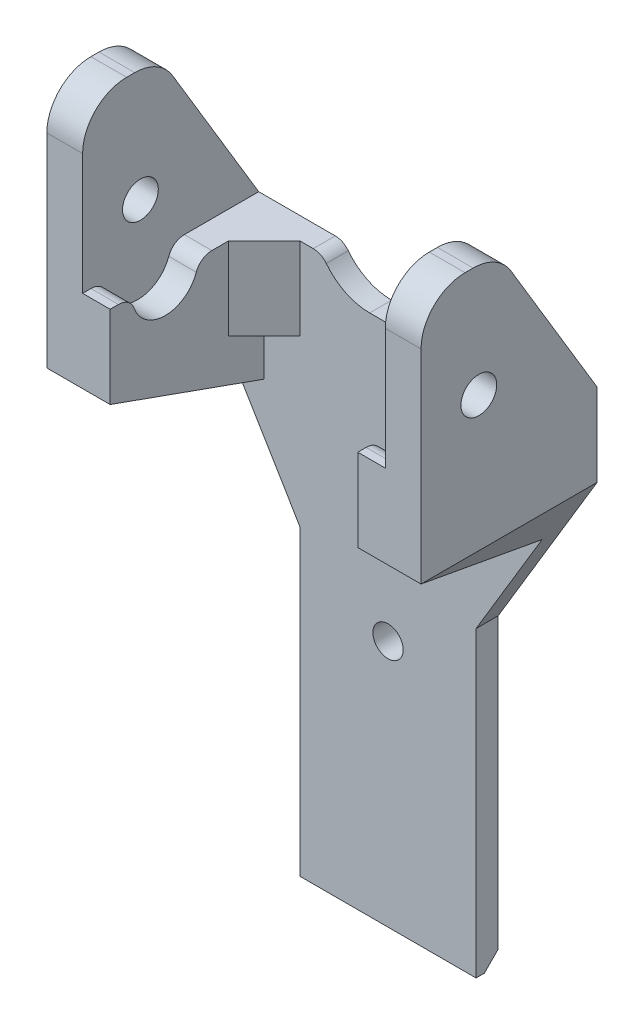
SolidWorks part; units mm, degrees
ref_plane "Plan de face" through (0, 0, 0) normal (0, 0, 1) x (1, 0, 0)
ref_plane "Plan de dessus" through (0, 0, 0) normal (0, 1, 0) x (1, 0, 0)
ref_plane "Plan de droite" through (0, 0, 0) normal (1, 0, 0) x (0, 0, -1)
sketch "Esquisse1" plane through (0, 0, 0) normal (0, 0, 1) x (1, 0, 0)
  line L1 (0, 0) -> (32, 0)
  line L2 (0, 0) -> (0, 100)
  line L3 (0, 100) -> (32, 100)
  line L4 (32, 0) -> (32, 100)
  dimension "D1" = 32
  dimension "D2" = 100
extrude "Boss.-Extru.1" add sketch "Esquisse1" along normal blind 4
chamfer "Chanfrein1" distance 2.5 angle 45 1 edges at (16, 0, 0)
fillet "Congé1" [suppressed] radius 10
sketch "Esquisse2" plane through (0, 0, 0) normal (0, 0, -1) x (-1, 0, 0)
  line L0 (-32, 2.5) -> (-32, 100) construction
  line L1 (-32, 85) -> (-50, 85)
  line L2 (-32, 85) -> (-32, 130)
  line L3 (-32, 130) -> (-50, 130)
  line L4 (-50, 85) -> (-50, 130)
  line L5 (-16, 100) -> (-16, 125.1629) construction
  line L6 (-32, 100) -> (0, 100) construction
  line L7 (18, 85) -> (18, 130)
  line L8 (0, 130) -> (18, 130)
  line L9 (0, 85) -> (0, 130)
  line L10 (0, 85) -> (18, 85)
  dimension "D1" = 15
  dimension "D2" = 18
  dimension "D3" = 30
extrude "Boss.-Extru.2" add sketch "Esquisse2" against normal blind 32
sketch "Esquisse3" plane through (-18, 0, 0) normal (-1, 0, 0) x (0, 0, 1)
  line L0 (32, 85) -> (0, 85) construction
  line L1 (4, 85) -> (4, 0) construction
  circle A0 centre (21.5, 109.5) radius 3.25
  dimension "D1" = 6.5
  dimension "D2" = 24.5
  dimension "D3" = 17.5
extrude "Enlèv. mat.-Extru.1" cut sketch "Esquisse3" against normal through all both and the other way through all
sketch "Esquisse4" plane through (0, 0, 32) normal (0, 0, 1) x (1, 0, 0)
  line L0 (-11.5, 100) -> (43.5, 100)
  line L1 (32, 100) -> (0, 100) construction
  line L2 (43.5, 100) -> (43.5, 132)
  line L3 (43.5, 132) -> (-11.5, 132)
  line L4 (16, 132) -> (16, 100) construction
  line L5 (-11.5, 100) -> (-11.5, 132)
  dimension "D1" = 55
  dimension "D2" = 32
extrude "Enlèv. mat.-Extru.2" cut sketch "Esquisse4" against normal through all both and the other way through all
sketch "Esquisse5" plane through (0, 100, 0) normal (0, 1, 0) x (1, 0, 0)
  line L0 (16, -4) -> (16, -34) construction
  line L1 (32, -4) -> (0, -4) construction
  line L2 (-6.5, -34) -> (38.5, -34)
  line L3 (38.5, -34) -> (38.5, -10.5)
  line L4 (38.5, -10.5) -> (-6.5, -10.5)
  line L5 (-6.5, -34) -> (-6.5, -10.5)
  point P8 (16, -10.5)
  dimension "D1" = 30
  dimension "D2" = 6.5
  dimension "D3" = 45
extrude "Enlèv. mat.-Extru.3" cut sketch "Esquisse5" against normal through all both and the other way through all
chamfer "Chanfrein2" distance 6.5 angle 45 2 edges at (0, 92.5, 10.5) (32, 92.5, 10.5)
sketch "Esquisse6" plane through (-6.5, 0, 0) normal (1, 0, 0) x (0, 0, -1)
  line L0 (0, 100) -> (-32, 100) construction
  line L1 (-32, 100) -> (-32, 130) construction
  line L2 (-28, 100) -> (-16, 100)
  arc A0 (-28, 100) -> (-16, 100) centre (-22, 100) ccw
  dimension "D1" = 6
  dimension "D2" = 10
extrude "Enlèv. mat.-Extru.4" cut sketch "Esquisse6" against normal up to vertex (5 mm away) up to point (-11.5, 100, 32)
extrude "Enlèv. mat.-Extru.6" cut sketch "Esquisse6<2>" along normal up to surface (50 mm away) from surface up to face at (43.5, 115, 16) starting at face at (38.5, 92.5, 21.25)
sketch "Esquisse6<2>" plane through (-6.5, 0, 0) normal (1, 0, 0) x (0, 0, -1) same geometry as "Esquisse6"
fillet "Congé2" radius 3 4 edges at (-9, 100, 28) (-9, 100, 16) (41, 100, 28) (41, 100, 16)
sketch "Esquisse7" plane through (50, 0, 0) normal (1, 0, 0) x (0, 0, -1)
  line L0 (0, 100) -> (-18, 130)
  line L1 (0, 130) -> (0, 85) construction
  line L2 (-32, 130) -> (0, 130) construction
  line L3 (-18, 130) -> (0, 130)
  line L4 (0, 130) -> (0, 100)
  line L5 (0, 100) -> (-13.5147, 100) construction
  point P6 (0, 0)
  point P9 (0, 101.5513)
  dimension "D1" = 18
extrude "Enlèv. mat.-Extru.7" cut sketch "Esquisse7" against normal through all both and the other way through all
fillet "Congé3" radius 8 4 edges at (46.75, 130, 18) (-14.75, 130, 18) (-14.75, 130, 32) (46.75, 130, 32)
sketch "Esquisse8" plane through (0, 0, 0) normal (0, 0, -1) x (-1, 0, 0)
  line L0 (-16, 100) -> (-16, 48.08) construction
  line L1 (-43.5, 100) -> (11.5, 100) construction
  line L2 (0, 55) -> (18, 85)
  line L3 (0, 85) -> (0, 2.5) construction
  line L4 (18, 85) -> (0, 85)
  line L5 (0, 85) -> (0, 55)
  line L6 (-32, 85) -> (-32, 55)
  line L7 (-50, 85) -> (-32, 85)
  line L8 (-32, 55) -> (-50, 85)
  dimension "D1" = 30
extrude "Boss.-Extru.3" add sketch "Esquisse8" against normal up to vertex (4 mm away) up to point (0, 85, 4)
sketch "Esquisse9" plane through (-18, 0, 0) normal (-1, 0, 0) x (0, 0, 1)
  line L0 (32, 85) -> (4, 85)
  line L1 (4, 85) -> (4, 75)
  line L2 (4, 55) -> (4, 85) construction
  line L3 (4, 75) -> (32, 85)
  dimension "D1" = 10
extrude "Boss.-Extru.4" add sketch "Esquisse9" against normal up to vertex (68 mm away) up to point (50, 85, 32)
sketch "Esquisse10" plane through (0, 0, 4) normal (0, 0, 1) x (1, 0, 0)
  line L0 (-6.5, 85) -> (-6.5, 75)
  line L1 (44, 75) -> (-12, 75) construction
  line L2 (-6.5, 75) -> (38.5, 75)
  line L3 (38.5, 75) -> (38.5, 85)
  line L4 (44, 75) -> (50, 85)
  line L5 (50, 85) -> (38.5, 85) construction
  line L6 (50, 75) -> (50, 85) construction
  line L7 (50, 85) -> (50, 75)
  line L8 (50, 75) -> (44, 75)
  line L9 (-12, 75) -> (-18, 85)
  line L10 (-18, 85) -> (-18, 75)
  line L11 (-18, 75) -> (-12, 75)
  line L12 (-6.5, 85) -> (38.5, 85)
extrude "Enlèv. mat.-Extru.8" cut sketch "Esquisse10" along normal through all
sketch "Esquisse11" plane through (0, 0, 4) normal (0, 0, 1) x (1, 0, 0)
  line L0 (16, 0) -> (16, 45) construction
  line L1 (0, 0) -> (32, 0) construction
  circle A0 centre (16, 45) radius 2.75
  dimension "D1" = 5.5
  dimension "D2" = 45
extrude "Enlèv. mat.-Extru.9" cut sketch "Esquisse11" against normal through all both and the other way through all
sketch "Esquisse12" plane through (0, 0, 0) normal (0, 0, -1) x (-1, 0, 0)
  line L0 (-43.5, 100) -> (11.5, 100) construction
  line L1 (-28, 100) -> (-4, 100)
  line L2 (-28, 100) -> (-28, 95)
  line L3 (-28, 95) -> (-4, 95)
  line L4 (-4, 100) -> (-4, 95)
  line L5 (-16, 95) -> (-16, 0) construction
  line L6 (0, 0) -> (-32, 0) construction
  dimension "D1" = 24
  dimension "D2" = 5
extrude "Enlèv. mat.-Extru.10" cut sketch "Esquisse12" against normal through all both and the other way through all
fillet "Congé4" radius 10 2 edges at (4, 95, 2) (28, 95, 2)
fillet "Congé5" radius 3 2 edges at (4, 100, 2) (28, 100, 2)
